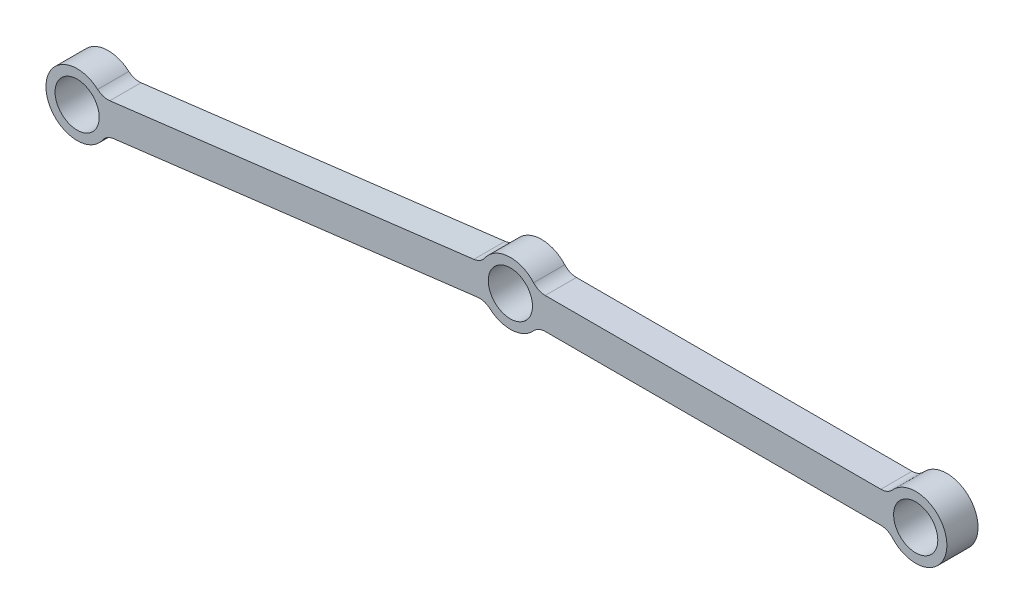
SolidWorks part; units mm, degrees
ref_plane "Front Plane" through (0, 0, 0) normal (0, 0, 1) x (1, 0, 0)
ref_plane "Top Plane" through (0, 0, 0) normal (0, 1, 0) x (1, 0, 0)
ref_plane "Right Plane" through (0, 0, 0) normal (1, 0, 0) x (0, 0, -1)
sketch "Sketch1" plane through (0, 0, 0) normal (0, 0, 1) x (1, 0, 0)
  line L0 (0, 0) -> (82.55, 0)
  line L1 (0, 0) -> (-88.2374, -10.8342)
  line L2 (-87.4635, -17.1369) -> (0.7739, -6.3027)
  line L3 (-89.0112, -4.5315) -> (-0.7739, 6.3027)
  line L4 (0, -6.35) -> (82.55, -6.35)
  line L5 (0, 6.35) -> (82.55, 6.35)
  line L6 (-83.166, -7.0127) -> (-5.8452, 2.4811)
  line L7 (5.4993, 3.175) -> (77.0507, 3.175)
  line L8 (-88.6243, -7.6829) -> (-0.3869, 3.1513) construction
  line L9 (0, 3.175) -> (82.55, 3.175) construction
  line L10 (-82.3921, -13.3153) -> (-5.0713, -3.8215)
  line L12 (5.4993, -3.175) -> (77.0507, -3.175)
  circle A0 centre (0, 0) radius 4.4996
  circle A1 centre (0, 0) radius 6.35
  circle A2 centre (-88.2374, -10.8342) radius 4.4996
  circle A3 centre (-88.2374, -10.8342) radius 6.35
  circle A5 centre (82.55, 0) radius 4.4996
  circle A6 centre (82.55, 0) radius 6.35
  dimension "D1" = 8.9992
  dimension "D2" = 12.7
  dimension "D5" = 8.9992
  dimension "D6" = 12.7
  dimension "D7" = 82.55
  dimension "D8" = 8.9992
  dimension "D9" = 12.7
  dimension "D3" = 88.9
  dimension "D4" = 173
  dimension "D10" = 3.175
  dimension "D11" = 3.175
  dimension "D12" = 3.175
extrude "Boss-Extrude2" add sketch "Sketch1" against normal blind 6.35 contours L1 A1 L0 A0 | L0 A1 L1 A0 | A3 A2 | A6 A5 | A3 L10 A1 L1 | A6 L0 A1 L12 | A6 L7 A1 L0 | A3 L1 A1 L6 region at (-0.2836, 4.6366, 0) region at (5.4248, -0.1416, 0) region at (41.275, 1.5938, 0) region at (41.275, -1.5938, 0) region at (-43.9245, -6.9985, 0) region at (-44.3128, -3.8357, 0) region at (76.5899, 1.597, 0) region at (-82.0785, -10.4575, 0)
fillet "Fillet2" radius 3.175 8 edges at (77.0507, 3.175, -3.175) (77.0507, -3.175, -3.175) (-5.0713, -3.8215, -3.175) (-5.8452, 2.4811, -3.175) (5.4993, 3.175, -3.175) (5.4993, -3.175, -3.175) (-82.3921, -13.3153, -3.175) (-83.166, -7.0127, -3.175)
